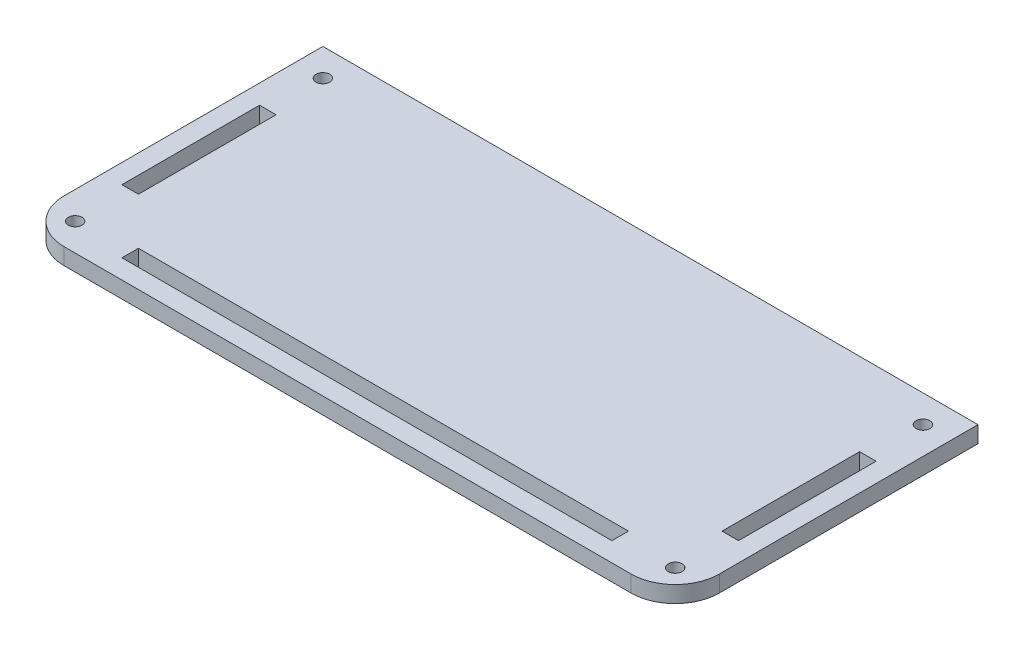
SolidWorks part; units mm, degrees
material "PVC rigido"
ref_plane "Piano frontale" through (0, 0, 0) normal (0, 0, 1) x (1, 0, 0)
ref_plane "Piano superiore" through (0, 0, 0) normal (0, 1, 0) x (1, 0, 0)
ref_plane "Piano destro" through (0, 0, 0) normal (1, 0, 0) x (0, 0, -1)
sketch "Schizzo1" plane through (0, 0, 0) normal (0, 1, 0) x (1, 0, 0)
  line L1 (-59.5, -27.5) -> (59.5, -27.5)
  line L2 (-59.5, -27.5) -> (-59.5, 27.5)
  line L3 (-59.5, 27.5) -> (59.5, 27.5)
  line L4 (59.5, -27.5) -> (59.5, 27.5)
  line L5 (-59.5, -27.5) -> (59.5, 27.5) construction
  line L6 (-59.5, 27.5) -> (59.5, -27.5) construction
  line L7 (67.5, 0) -> (59.5, 0) construction
  line L8 (67.5, -27.5) -> (67.5, -18) construction
  line L9 (-59.5, 0) -> (-67.5, 0) construction
  line L10 (-67.5, 21.5) -> (-67.5, 12) construction
  point P0 (0, 0)
  dimension "D1" = 8
  dimension "D2" = 55
extrude "Estrusione-Estrusione1" add sketch "Schizzo1" along normal blind 3
hole_wizard "Foro filettato M3x0.5-1" positions "Schizzo3" profile "Schizzo2" tap size "M3x0.5" standard "Ansi Metric" end condition through all
sketch "Schizzo3" plane through (0, 3, 0) normal (0, 1, 0) x (1, 0, 0)
  line L16 (54.5, -22.5) -> (54.5, 22.5)
  line L17 (54.5, 22.5) -> (-54.5, 22.5)
  line L18 (-54.5, 22.5) -> (-54.5, -22.5)
  line L19 (-54.5, -22.5) -> (54.5, -22.5)
  line L20 (54.5, -22.5) -> (54.5, 22.5) construction
  line L21 (54.5, 22.5) -> (-54.5, 22.5) construction
  line L22 (-54.5, 22.5) -> (-54.5, -22.5) construction
  line L23 (-54.5, -22.5) -> (54.5, -22.5) construction
  point P0 (-54.5, -22.5)
  point P2 (54.5, -22.5)
  point P4 (54.5, 22.5)
  point P6 (-54.5, 22.5)
  dimension "D1" = 5
sketch "Schizzo2" plane through (-54.5, 3, 22.5) normal (1, 0, 0) x (0, 0, 1)
  line L0 (0, 0) -> (0, 3)
  line L1 (0, 3) -> (1.25, 3)
  line L2 (1.25, 3) -> (1.25, 0)
  line L5 (1.25, 0) -> (0, 0)
  line L11 (0, -6.35) -> (0, 107.95) construction
  dimension "Thru Tap Drill Dia." = 2.5
  dimension "Thru Tap Drill Depth" = 3
cosmetic thread "Filettatura del foro1" parameters "D2"=3
cosmetic thread "Filettatura del foro2" parameters "D2"=3
cosmetic thread "Filettatura del foro3" parameters "D2"=3
cosmetic thread "Filettatura del foro4" parameters "D2"=3
sketch "Schizzo4" plane through (0, 3, 0) normal (0, 1, 0) x (1, 0, 0)
  line L0 (-54.5, -22.5) -> (-44.5, -22.5) construction
  line L1 (-44.5, -22.5) -> (44.5, -22.5) construction
  line L2 (44.5, -22.5) -> (54.5, -22.5) construction
  line L3 (54.5, -22.5) -> (54.5, -12.5) construction
  line L4 (54.5, -12.5) -> (54.5, 12.5) construction
  line L5 (54.5, 12.5) -> (54.5, 22.5) construction
  line L6 (-54.5, -22.5) -> (-54.5, -12.5) construction
  line L7 (-54.5, -12.5) -> (-54.5, 12.5) construction
  line L8 (-54.5, 12.5) -> (-54.5, 22.5) construction
  line L10 (-44.5, -24) -> (44.5, -24)
  line L11 (-44.5, -24) -> (-44.5, -21)
  line L12 (-44.5, -21) -> (44.5, -21)
  line L13 (44.5, -24) -> (44.5, -21)
  line L14 (53, 12.5) -> (56, 12.5)
  line L15 (53, 12.5) -> (53, -12.5)
  line L16 (53, -12.5) -> (56, -12.5)
  line L17 (56, 12.5) -> (56, -12.5)
  line L18 (-53, -12.5) -> (-56, -12.5)
  line L19 (-53, -12.5) -> (-53, 12.5)
  line L20 (-53, 12.5) -> (-56, 12.5)
  line L21 (-56, -12.5) -> (-56, 12.5)
  dimension "D1" = 10
  dimension "D2" = 3
extrude "Taglio-Estrusione1" cut sketch "Schizzo4" against normal through all
fillet "Raccordo1" radius 8 2 edges at (-59.5, 1.5, 27.5) (59.5, 1.5, 27.5)
